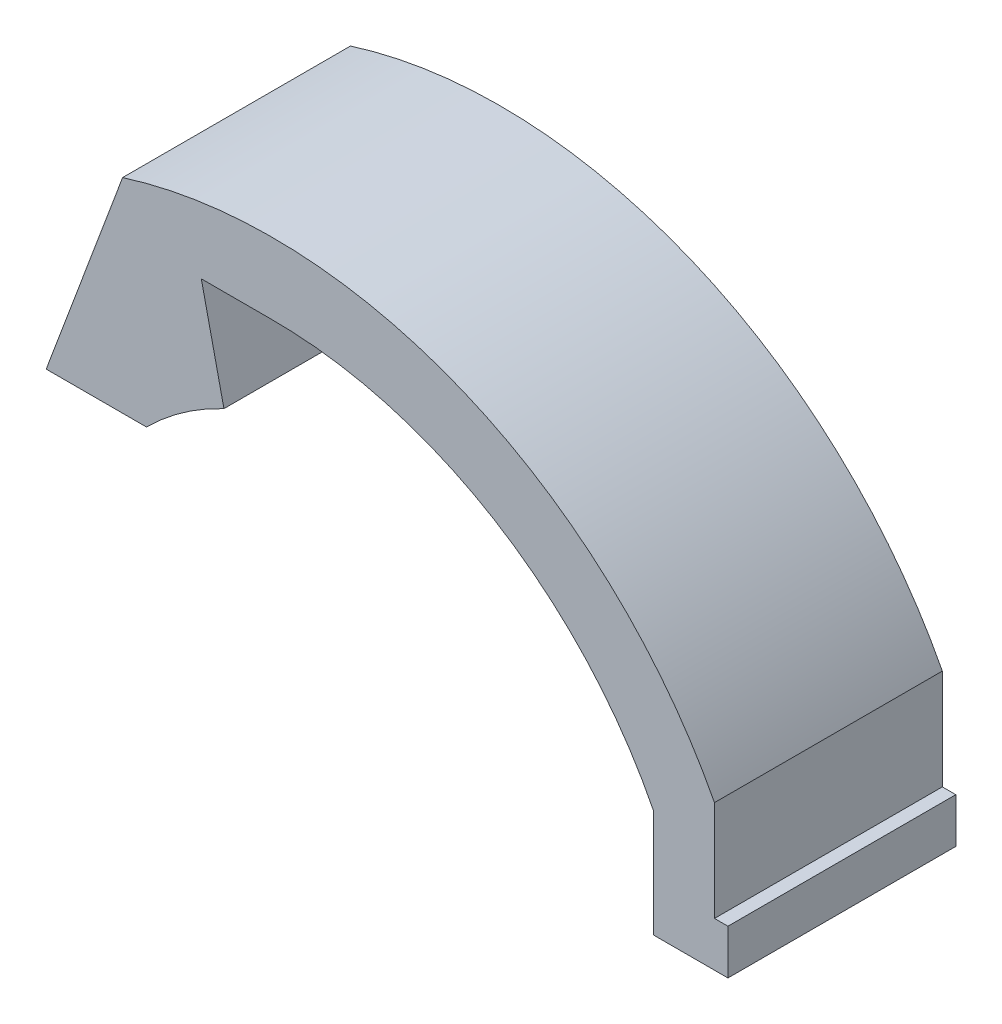
SolidWorks part; units mm, degrees
ref_plane "Front Plane" through (0, 0, 0) normal (0, 0, 1) x (1, 0, 0)
ref_plane "Top Plane" through (0, 0, 0) normal (0, 1, 0) x (1, 0, 0)
ref_plane "Right Plane" through (0, 0, 0) normal (1, 0, 0) x (0, 0, -1)
sketch "Sketch2" plane through (0, 0, 0) normal (0, 0, 1) x (1, 0, 0)
  line L8 (-36.9786, 13.785) -> (-38.24, 19.4237)
  line L17 (-13.0378, 0.35) -> (-13.0378, 6.35)
  line L36 (-38.24, 19.4237) -> (-34.49, 19.4237)
  line L38 (-41.2918, 10.7407) -> (-46.8848, 10.7407)
  line L39 (-46.8848, 10.7407) -> (-42.6259, 22.1174)
  line L51 (-13.0378, 0.35) -> (-11.4125, 0.35)
  line L52 (-9.6376, 8.4404) -> (-9.6376, 2.85)
  line L58 (-11.4125, 0.35) -> (-8.8876, 0.35)
  line L60 (-9.6376, 2.85) -> (-8.8876, 2.85)
  line L61 (-8.8876, 0.35) -> (-8.8876, 2.85)
  arc A3 (-41.2918, 10.7407) -> (-36.9786, 13.785) centre (-30.48, 0) cw
  arc A6 (-9.6376, 8.4404) -> (-42.6259, 22.1174) centre (-34.2728, -4.3569) ccw
  arc A8 (-13.0378, 6.35) -> (-34.49, 19.4237) centre (-34.2728, -4.3569) ccw
  dimension "D4" = 0.75
  dimension "D5" = 2.5
extrude "Boss-Extrude2" add sketch "Sketch2" against normal blind 12.7 separate body
